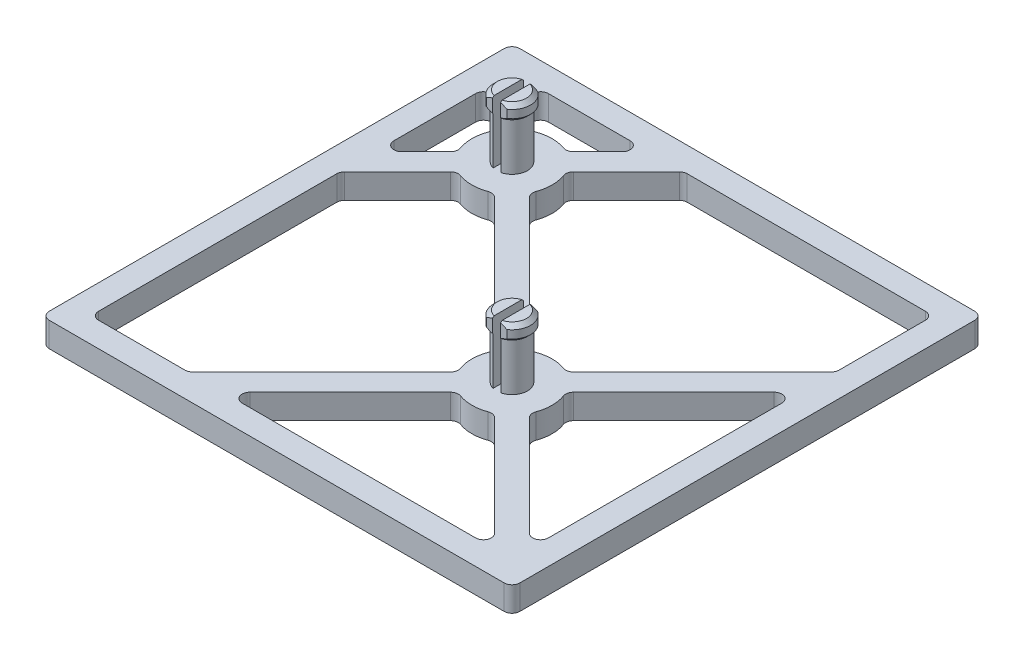
SolidWorks part; units mm, degrees
ref_plane "Front Plane" through (0, 0, 0) normal (0, 0, 1) x (1, 0, 0)
ref_plane "Top Plane" through (0, 0, 0) normal (0, 1, 0) x (1, 0, 0)
ref_plane "Right Plane" through (0, 0, 0) normal (1, 0, 0) x (0, 0, -1)
sketch "Base Profile" plane through (0, 0, 0) normal (0, 1, 0) x (1, 0, 0)
  line L1 (-38.1, -38.1) -> (38.1, -38.1)
  line L2 (-38.1, -38.1) -> (-38.1, 38.1)
  line L3 (-38.1, 38.1) -> (38.1, 38.1)
  line L4 (38.1, -38.1) -> (38.1, 38.1)
  line L5 (-38.1, -38.1) -> (38.1, 38.1) construction
  line L6 (-38.1, 38.1) -> (38.1, -38.1) construction
  point P0 (0, 0)
  dimension "D1" = 76.2
  dimension "D2" = 76.2
extrude "Base" add sketch "Base Profile" along normal mid plane 4
sketch "Connector Profile" plane through (0, 2, 0) normal (0, 1, 0) x (1, 0, 0)
  line L0 (-21.59, 21.59) -> (9.3021, -9.3021) construction
  line L1 (-38.1, -38.1) -> (38.1, -38.1) construction
  line L2 (38.1, 38.1) -> (-38.1, 38.1) construction
  line L4 (-38.1, 38.1) -> (-38.1, -38.1) construction
  circle A0 centre (-21.59, 21.59) radius 2.5
  circle A1 centre (9.3021, -9.3021) radius 2.5
  dimension "D1" = 5
  dimension "D2" = 5
  dimension "D5" = 16.51
  dimension "D6" = 16.51
  dimension "D3" = 43.688
  dimension "D4" = 45
extrude "Connector Body" add sketch "Connector Profile" along normal blind 7.5
sketch "Cutout Profile" plane through (0, 2, 0) normal (0, 1, 0) x (1, 0, 0)
  line L0 (-38.1, 38.1) -> (-38.1, -38.1) construction
  line L1 (-31.2716, 34.1) -> (-11.9084, 34.1)
  line L2 (-34.1, 31.2716) -> (-34.1, 11.9084)
  line L3 (-34.1, -34.1) -> (-18.3243, -34.1)
  line L4 (34.1, 34.1) -> (34.1, 18.3243)
  line L5 (38.1, 38.1) -> (-38.1, 38.1) construction
  line L6 (38.1, -38.1) -> (38.1, 38.1) construction
  line L7 (-38.1, -38.1) -> (38.1, -38.1) construction
  line L8 (-31.2716, 34.1) -> (-24.549, 27.3774)
  line L9 (-34.1, 31.2716) -> (-27.3774, 24.549)
  line L10 (15.0895, -6.3431) -> (34.1, 12.6674)
  line L11 (-34.1, 11.9084) -> (-34.1, 6.2516) construction
  line L12 (-34.1, 6.2516) -> (-24.549, 15.8026)
  line L13 (-34.1, 11.9084) -> (-27.3774, 18.631)
  line L14 (-18.3243, -34.1) -> (3.5147, -12.2611)
  line L15 (-12.6674, -34.1) -> (6.3431, -15.0895)
  line L16 (-11.9084, 34.1) -> (-6.2516, 34.1) construction
  line L17 (-34.1, 9.08) -> (-9.08, 34.1) construction
  line L18 (-6.2516, 34.1) -> (34.1, 34.1)
  line L19 (-18.631, 15.8026) -> (3.5147, -6.3431)
  line L20 (-34.1, 31.2716) -> (-31.2716, 34.1) construction
  line L21 (-18.631, 27.3774) -> (-11.9084, 34.1)
  line L22 (-15.8026, 24.549) -> (-6.2516, 34.1)
  line L23 (31.2716, -34.1) -> (34.1, -31.2716) construction
  line L24 (34.1, -31.2716) -> (32.6858, -32.6858) construction
  line L25 (-34.1, 6.2516) -> (-34.1, -34.1)
  line L26 (-12.6674, -34.1) -> (31.2716, -34.1)
  line L27 (12.2611, -15.0895) -> (31.2716, -34.1)
  line L28 (12.2611, -3.5147) -> (34.1, 18.3243)
  line L29 (15.0895, -12.2611) -> (34.1, -31.2716)
  line L30 (34.1, 12.6674) -> (34.1, -31.2716)
  line L31 (-15.8026, 18.631) -> (6.3431, -3.5147)
  line L32 (32.6858, -32.6858) -> (-32.6858, 32.6858) construction
  line L33 (34.1, 15.4958) -> (-15.4958, -34.1) construction
  line L34 (-18.3243, -34.1) -> (-12.6674, -34.1) construction
  arc A0 (-15.8026, 18.631) -> (-15.8026, 24.549) centre (-21.59, 21.59) ccw
  arc A1 (12.2611, -3.5147) -> (6.3431, -3.5147) centre (9.3021, -9.3021) ccw
  circle A2 centre (9.3021, -9.3021) radius 2.5 construction
  circle A3 centre (-21.59, 21.59) radius 2.5 construction
  arc A4 (6.3431, -15.0895) -> (12.2611, -15.0895) centre (9.3021, -9.3021) ccw
  arc A5 (3.5147, -6.3431) -> (3.5147, -12.2611) centre (9.3021, -9.3021) ccw
  arc A6 (15.0895, -12.2611) -> (15.0895, -6.3431) centre (9.3021, -9.3021) ccw
  arc A7 (-18.631, 27.3774) -> (-24.549, 27.3774) centre (-21.59, 21.59) ccw
  arc A8 (-27.3774, 24.549) -> (-27.3774, 18.631) centre (-21.59, 21.59) ccw
  arc A9 (-24.549, 15.8026) -> (-18.631, 15.8026) centre (-21.59, 21.59) ccw
  point P42 (-21.59, 21.59)
  point P46 (9.3021, -9.3021)
  point P47 (-9.08, 34.1)
  dimension "D1" = 4
  dimension "D2" = 4
  dimension "D3" = 4
  dimension "D4" = 4
  dimension "D5" = 4
  dimension "D6" = 4
  dimension "D7" = 4
  dimension "D8" = 4
  dimension "D9" = 4
  dimension "D10" = 4
extrude "Base Cutout" cut sketch "Cutout Profile" against normal up to surface (4 mm away) up to face at (0, -2, 0)
fillet "Base Fillet" radius 1.27 34 edges at (34.1, 0, -34.1) (34.1, 0, -18.3243) (12.2611, 0, 3.5147) (6.3431, 0, 3.5147) (-6.2516, 0, -34.1) (-15.8026, 0, -24.549) (-15.8026, 0, -18.631) (-31.2716, 0, -34.1) (-11.9084, 0, -34.1) (-18.631, 0, -27.3774) (-24.549, 0, -27.3774) (-27.3774, 0, -24.549) (-34.1, 0, -31.2716) (-34.1, 0, -11.9084) (-34.1, 0, -6.2516) (-27.3774, 0, -18.631) (-24.549, 0, -15.8026) (-18.631, 0, -15.8026) (3.5147, 0, 6.3431) (3.5147, 0, 12.2611) (-34.1, 0, 34.1) (-18.3243, 0, 34.1) (34.1, 0, -12.6674) (34.1, 0, 31.2716) (15.0895, 0, 6.3431) (15.0895, 0, 12.2611) (6.3431, 0, 15.0895) (12.2611, 0, 15.0895) (-12.6674, 0, 34.1) (31.2716, 0, 34.1) (38.1, 0, -38.1) (-38.1, 0, -38.1) (38.1, 0, 38.1) (-38.1, 0, 38.1)
sketch "Head Profile" plane through (0, 9.5, 0) normal (0, 1, 0) x (1, 0, 0)
  circle A0 centre (-21.59, 21.59) radius 3
  circle A1 centre (9.3021, -9.3021) radius 3
  circle A2 centre (-21.59, 21.59) radius 2.5 construction
  circle A3 centre (9.3021, -9.3021) radius 2.5 construction
  dimension "D1" = 6
  dimension "D2" = 6
extrude "Connector Head" add sketch "Head Profile" along normal blind 2.6
chamfer "Connector Head Chamfer" distance 0.65 angle 45 4 edges at (-21.59, 9.5, -18.59) (-21.59, 12.1, -18.59) (9.3021, 9.5, 12.3021) (9.3021, 12.1, 12.3021)
sketch "Gap Profile" plane through (0, 12.1, 0) normal (0, 1, 0) x (1, 0, 0)
  line L0 (-22.24, 24.5187) -> (-22.24, 18.6613)
  line L1 (-20.94, 24.5187) -> (-20.94, 18.6613)
  line L2 (-22.24, 21.59) -> (-20.94, 21.59) construction
  line L3 (8.6521, -6.3733) -> (8.6521, -12.2308)
  line L4 (9.9521, -6.3733) -> (9.9521, -12.2308)
  line L5 (8.6521, -9.3021) -> (9.9521, -9.3021) construction
  circle A0 centre (-21.59, 21.59) radius 3 construction
  arc A1 (-20.94, 24.5187) -> (-22.24, 24.5187) centre (-21.59, 21.59) ccw
  circle A2 centre (9.3021, -9.3021) radius 3 construction
  arc A3 (9.9521, -6.3733) -> (8.6521, -6.3733) centre (9.3021, -9.3021) ccw
  arc A4 (8.6521, -12.2308) -> (9.9521, -12.2308) centre (9.3021, -9.3021) ccw
  arc A5 (-22.24, 18.6613) -> (-20.94, 18.6613) centre (-21.59, 21.59) ccw
  dimension "D1" = 1.3
  dimension "D2" = 1.3
extrude "Connector Gap" cut sketch "Gap Profile" against normal up to surface (10.1 mm away) up to face at (-21.59, 2, -24.09)
sketch "Trim Profile" plane through (0, 12.1, 0) normal (0, 1, 0) x (1, 0, 0)
  line L0 (7.6438, -6.8021) -> (10.9604, -6.8021)
  line L1 (9.3021, -6.8021) -> (9.3021, -11.8021) construction
  line L2 (7.6438, -11.8021) -> (10.9604, -11.8021)
  line L3 (-23.2483, 24.09) -> (-19.9317, 24.09)
  line L4 (-23.2483, 19.09) -> (-19.9317, 19.09)
  line L5 (-21.59, 24.09) -> (-21.59, 19.09) construction
  arc A0 (7.6438, -11.8021) -> (10.9604, -11.8021) centre (9.3021, -9.3021) ccw
  arc A1 (9.9521, -12.2308) -> (9.9521, -6.3733) centre (9.3021, -9.3021) ccw construction
  arc A2 (10.9604, -6.8021) -> (7.6438, -6.8021) centre (9.3021, -9.3021) ccw
  arc A3 (-23.2483, 19.09) -> (-19.9317, 19.09) centre (-21.59, 21.59) ccw
  arc A4 (-20.94, 18.6613) -> (-20.94, 24.5187) centre (-21.59, 21.59) ccw construction
  arc A5 (-22.24, 24.5187) -> (-22.24, 18.6613) centre (-21.59, 21.59) ccw construction
  arc A6 (-19.9317, 24.09) -> (-23.2483, 24.09) centre (-21.59, 21.59) ccw
  dimension "D2" = 5
  dimension "D1" = 5
extrude "Trim Head" cut sketch "Trim Profile" against normal up to surface (10.1 mm away) up to face at (-23.165, 2, -21.59)
equation "\"D2@Cutout Profile\" = \"D1@Cutout Profile\""
equation "\"D8@Cutout Profile\" = \"D1@Cutout Profile\""
equation "\"D7@Cutout Profile\" = \"D1@Cutout Profile\""
equation "\"D5@Cutout Profile\" = \"D1@Cutout Profile\""
equation "\"D4@Cutout Profile\" = \"D1@Cutout Profile\""
equation "\"D6@Cutout Profile\" = \"D1@Cutout Profile\""
equation "\"D3@Cutout Profile\" = \"D1@Cutout Profile\""
equation "\"D9@Cutout Profile\" = \"D1@Cutout Profile\""
equation "\"D10@Cutout Profile\" = \"D1@Cutout Profile\""
